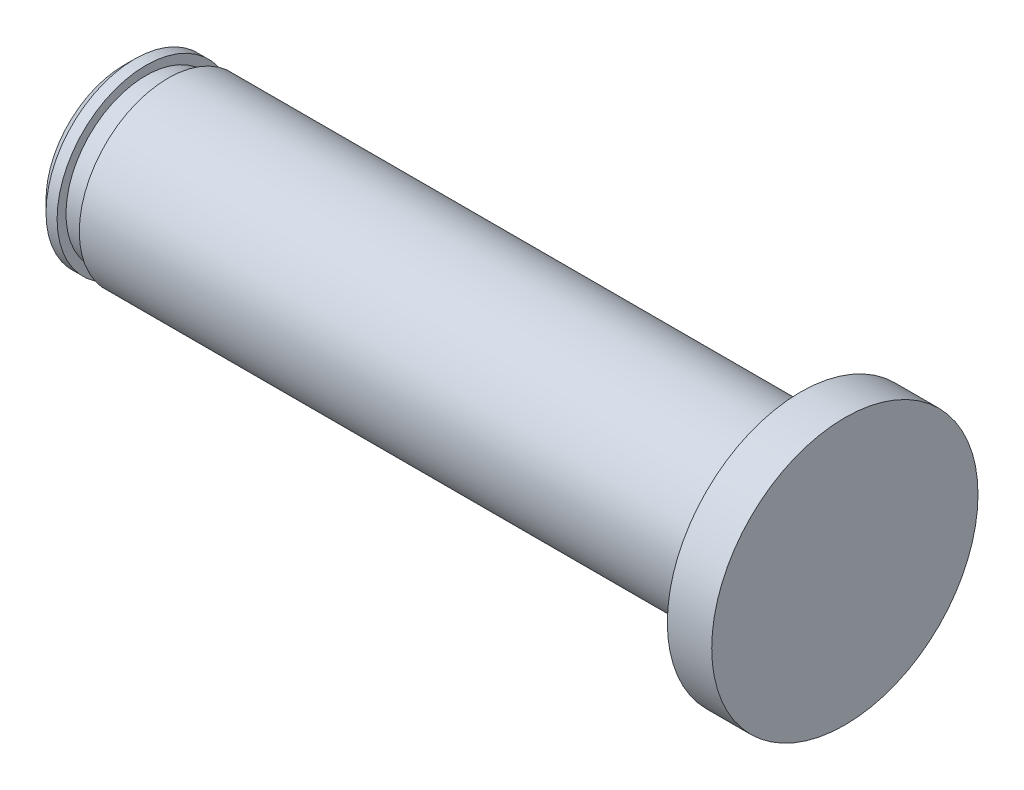
SolidWorks part; units mm, degrees
ref_plane "Спереди" through (0, 0, 0) normal (0, 0, 1) x (1, 0, 0)
ref_plane "Сверху" through (0, 0, 0) normal (0, 1, 0) x (1, 0, 0)
ref_plane "Справа" through (0, 0, 0) normal (1, 0, 0) x (0, 0, -1)
sketch "Эскиз1" plane through (0, 0, 0) normal (0, 0, 1) x (1, 0, 0)
  line L0 (0, 0) -> (-32.5, 0)
  line L1 (-32.5, 0) -> (-32.5, 4)
  line L2 (-32.5, 4) -> (-31.5, 4)
  line L3 (-31.5, 4) -> (-31.5, 3.6)
  line L4 (-31.5, 3.6) -> (-30.5, 3.6)
  line L5 (-30.5, 3.6) -> (-30.5, 4)
  line L6 (-30.5, 4) -> (-2, 4)
  line L7 (-2, 4) -> (-2, 6)
  line L8 (-2, 6) -> (0, 6)
  line L9 (0, 6) -> (0, 0)
  line L10 (-32.5, 0) -> (-24.8571, 0) construction
  line L11 (-32, 0) -> (-50032, 0) construction
  line L12 (-30.5, 4) -> (-30.5, -4) construction
  dimension "D1" = 8
  dimension "D3" = 2
  dimension "D4" = 2
  dimension "D5" = 1
  dimension "D6" = 1
  dimension "D7" = 7.2
revolve "Повернуть1" add sketch "Эскиз1" angle 360 about L10
chamfer "Фаска1" distance 0.5 angle 45 1 edges at (-32.5, -4, 0)
equation "\"Диаметр вала\" = 8  '!!!"
equation "\"Длина вала\" = 28"
equation "\"D1@Эскиз1\"=\"Диаметр вала\""
